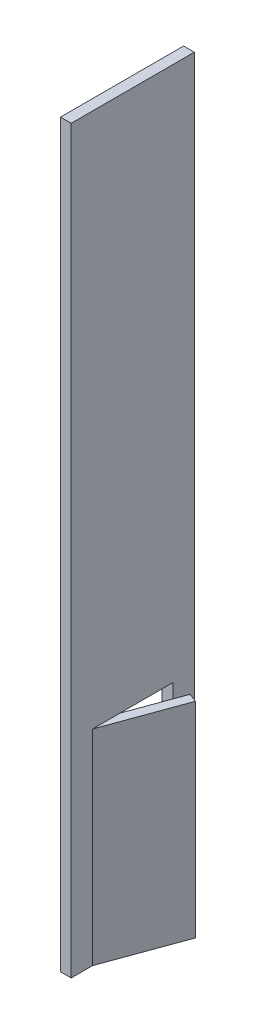
SolidWorks part; units mm, degrees
material "6061-T6 (SS)"
ref_plane "Front" through (0, 0, 0) normal (0, 0, 1) x (1, 0, 0)
ref_plane "Top" through (0, 0, 0) normal (0, 1, 0) x (1, 0, 0)
ref_plane "Right" through (0, 0, 0) normal (1, 0, 0) x (0, 0, -1)
sketch "Sketch1" plane through (0, 0, 0) normal (0, 1, 0) x (1, 0, 0)
  line L1 (-50.8, 584.2) -> (50.8, 584.2)
  line L2 (-50.8, 584.2) -> (-50.8, -584.2)
  line L3 (-50.8, -584.2) -> (50.8, -584.2)
  line L4 (50.8, 584.2) -> (50.8, -584.2)
  line L5 (-50.8, 584.2) -> (50.8, -584.2) construction
  line L6 (-50.8, -584.2) -> (50.8, 584.2) construction
  point P0 (0, 0)
  dimension "D1" = 1168.4
  dimension "D2" = 101.6
extrude "Boss-Extrude1" add sketch "Sketch1" along normal blind 7023.1
sketch "Sketch2" plane through (50.8, 0, 0) normal (1, 0, 0) x (0, 0, -1)
  line L0 (584.2, 7023.1) -> (584.2, 0) construction
  line L1 (584.2, 0) -> (431.8, 0)
  line L2 (584.2, 0) -> (584.2, 2286)
  line L3 (584.2, 2286) -> (431.8, 2286)
  line L4 (431.8, 0) -> (431.8, 2286)
  line L6 (-584.2, 0) -> (584.2, 0) construction
  dimension "D1" = 152.4
  dimension "D2" = 2286
extrude "Cut-Extrude1" [suppressed] cut sketch "Sketch2" against normal through all
sketch "Sketch3" plane through (50.8, 0, 0) normal (1, 0, 0) x (0, 0, -1)
  line L2 (-381, 1944.6548) -> (-381, 0)
  line L4 (377.825, 0) -> (812.8, 0) construction
  line L5 (381, 0) -> (-381, 0)
  line L6 (584.2, 7023.1) -> (584.2, 0) construction
  line L12 (381, 1944.6548) -> (381, 0)
  line L13 (-381, 1944.6548) -> (381, 1944.6548)
  dimension "D2" = 1944.6548
  dimension "D1" = 762
  dimension "D3" = 203.2
extrude "Cut-Extrude2" cut sketch "Sketch3" against normal through all
sketch "Sketch4" [suppressed] plane through (-76.2, 0, 0) normal (-1, 0, 0) x (0, 0, 1)
  line L0 (-584.2, 6400.8) -> (584.2, 6400.8) construction
  line L1 (584.2, 6400.8) -> (584.2, 0) construction
  circle A0 centre (177.8, 5994.4) radius 152.4
  dimension "D1" = 304.8
  dimension "D2" = 406.4
  dimension "D3" = 406.4
extrude "Cut-Extrude3" [suppressed] cut sketch "Sketch4" against normal through all and the other way through all
sketch "Sketch5" [suppressed] plane through (-76.2, 0, 0) normal (-1, 0, 0) x (0, 0, 1)
  line L0 (584.2, 6400.8) -> (584.2, 0) construction
  line L1 (-584.2, 0) -> (584.2, 0) construction
  circle A0 centre (177.8, 406.4) radius 152.4
  dimension "D1" = 304.8
  dimension "D2" = 406.4
  dimension "D3" = 406.4
extrude "Cut-Extrude4" [suppressed] cut sketch "Sketch5" against normal through all
sketch "Sketch6" [suppressed] plane through (50.8, 0, 0) normal (1, 0, 0) x (0, 0, -1)
  line L0 (-584.2, 7023.1) -> (-584.2, 0) construction
  line L1 (584.2, 0) -> (-584.2, 0)
  line L2 (584.2, 0) -> (584.2, 4267.2)
  line L3 (584.2, 4267.2) -> (-584.2, 4267.2)
  line L4 (-584.2, 0) -> (-584.2, 4267.2)
  dimension "D1" = 4267.2
extrude "Cut-Extrude5" [suppressed] cut sketch "Sketch6" against normal through all
sketch "Sketch7" [suppressed] plane through (50.8, 0, 0) normal (1, 0, 0) x (0, 0, -1)
  line L1 (-584.2, 0) -> (215.9, 0)
  line L2 (-584.2, 0) -> (-584.2, 4267.2)
  line L3 (-584.2, 4267.2) -> (215.9, 4267.2)
  line L4 (215.9, 0) -> (215.9, 4267.2)
  dimension "D1" = 4267.2
  dimension "D2" = 800.1
extrude "Cut-Extrude6" [suppressed] cut sketch "Sketch7" against normal through all
sketch "Sketch8" plane through (0, 1944.6548, 0) normal (0, -1, 0) x (1, 0, 0)
  line L0 (50.8, 381) -> (311.4193, -335.0458)
  line L1 (311.4193, -335.0458) -> (227.8807, -365.4514)
  line L2 (227.8807, -365.4514) -> (-32.7387, 350.5944)
  line L3 (-32.7387, 350.5944) -> (50.8, 381)
  line L4 (50.8, -381) -> (50.8, 381) construction
  dimension "D1" = 762
  dimension "D2" = 88.9
  dimension "D3" = 20
extrude "Boss-Extrude2" add sketch "Sketch8" along normal up to surface (1944.6548 mm away) separate body up to face at (0, 0, 482.6)
